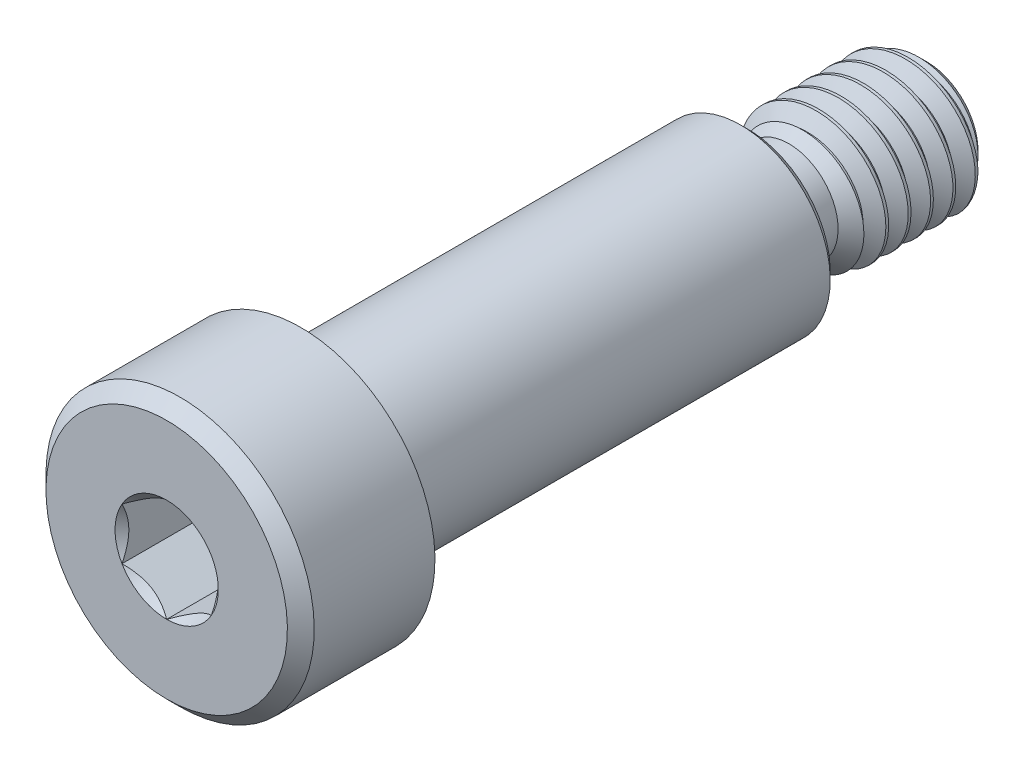
SolidWorks part; units mm, degrees
ref_plane "Front Plane" through (0, 0, 0) normal (0, 0, 1) x (1, 0, 0)
ref_plane "Top Plane" through (0, 0, 0) normal (0, 1, 0) x (1, 0, 0)
ref_plane "Right Plane" through (0, 0, 0) normal (1, 0, 0) x (0, 0, -1)
sketch "Sketch2" plane through (0, 0, 0) normal (1, 0, 0) x (0, 0, -1)
  line L0 (-13.4937, 0) -> (13.4937, 0) construction
  line L1 (-13.4937, 0) -> (-13.4937, 4.7625)
  line L2 (-13.4937, 4.7625) -> (-8.7312, 4.7625)
  line L3 (-8.7312, 4.7625) -> (-8.7313, 3.175)
  line L4 (-8.7313, 3.175) -> (7.1437, 3.175)
  line L5 (7.1437, 2.413) -> (13.4937, 2.413)
  line L6 (13.4937, 2.413) -> (13.4937, 0)
  line L7 (13.4441, 2.4989) -> (13.841, 1.8115) construction
  line L8 (13.841, 1.8115) -> (14.2379, 2.4989) construction
  line L9 (14.2379, 2.4989) -> (13.4441, 2.4989) construction
  line L10 (13.4937, 2.413) -> (14.1883, 2.413) construction
  line L11 (13.841, 2.4989) -> (13.841, 2.413) construction
  line L12 (13.841, 2.413) -> (13.841, 1.8974) construction
  line L13 (13.841, 1.8974) -> (13.841, 1.8115) construction
  line L14 (13.7914, 1.8974) -> (13.8906, 1.8974)
  line L15 (13.4689, 2.456) -> (14.2131, 2.456)
  line L16 (13.8906, 1.8974) -> (14.2131, 2.456)
  line L17 (13.7914, 1.8974) -> (13.4689, 2.456)
  line L18 (13.4937, 0) -> (13.4937, -2.413) construction
  line L19 (7.1437, -3.175) -> (7.1437, 0) construction
  line L20 (7.1437, 0) -> (7.1437, 3.175) construction
  line L21 (-13.4937, 0) -> (-13.4937, -4.7625) construction
  line L22 (8.5947, 1.7494) -> (8.5947, -1.7494) construction
  line L23 (13.4937, 0) -> (8.5947, 0) construction
  point P12 (11.5094, -2.413)
  point P22 (13.841, 2.456)
  point P23 (5.8737, 0)
  point P25 (-5.8737, 0)
  point P26 (-8.7312, -4.7625)
  point P29 (7.1437, -3.175)
  point P40 (8.5947, 0)
  dimension "Head Height" = 4.7625
  dimension "Shoulder Diameter" = 6.35
  dimension "Screw Size Decimal Equivalent" = 4.826
  dimension "Thread Length" = 6.35
  dimension "Head Diameter" = 9.525
  dimension "Pitch" = 0.7937
  dimension "D2" = 0.0992
  dimension "D1" = 1.9844
  dimension "D3" = 7.62
  dimension "D4" = 7.62
  dimension "Shoulder Length" = 15.875
  dimension "Flat" = 1.451
  dimension "Flat OD" = 3.4988
sketch "Sketch3" plane through (0, 0, 0) normal (0, 0, 1) x (1, 0, 0)
  line L1 (0, 1.8331) -> (-1.5875, 0.9165)
  line L2 (-1.5875, 0.9165) -> (-1.5875, -0.9165)
  line L3 (-1.5875, -0.9165) -> (0, -1.8331)
  line L4 (0, -1.8331) -> (1.5875, -0.9165)
  line L5 (1.5875, -0.9165) -> (1.5875, 0.9165)
  line L6 (1.5875, 0.9165) -> (0, 1.8331)
  circle A0 centre (0, 0) radius 1.5875 construction
  dimension "Drive Size" = 3.175
sketch "Sketch4" plane through (0, 0, 0) normal (1, 0, 0) x (0, 0, -1)
  line L0 (-8.7312, 4.7625) -> (-13.0175, 4.7625)
  line L1 (-13.0175, 4.7625) -> (-13.4937, 4.2862)
  line L2 (-8.7312, 4.7625) -> (-8.7313, 3.175)
  line L7 (-13.4937, 0) -> (13.4937, 0) construction
  line L8 (-8.7313, 3.175) -> (6.8897, 3.175)
  line L9 (6.8897, 3.175) -> (7.1437, 2.921)
  line L10 (7.1437, 2.921) -> (7.1437, 0)
  line L11 (7.1437, 3.175) -> (7.1437, 2.921) construction
  line L12 (7.1437, 2.921) -> (7.1437, 2.667) construction
  line L13 (7.1437, 2.667) -> (7.1437, 2.413) construction
  line L14 (-13.4937, 4.2862) -> (-13.4937, 0)
  line L16 (-13.4937, 0) -> (7.1437, 0)
  line L18 (-13.4937, 4.7625) -> (-8.7312, 4.7625) construction
  dimension "D3" = 45
  dimension "D5" = 8.5725
  dimension "D1" = 45
revolve "Revolve1" add sketch "Sketch4" angle 360 about L16
sketch "Sketch5" plane through (0, 0, 13.4937) normal (0, 0, 1) x (1, 0, 0)
  line L0 (1.5875, 0.9165) -> (0, 1.8331) construction
  line L1 (1.5875, -0.9165) -> (1.5875, 0.9165) construction
  line L2 (0, -1.8331) -> (1.5875, -0.9165) construction
  line L3 (-1.5875, -0.9165) -> (0, -1.8331) construction
  line L4 (-1.5875, 0.9165) -> (-1.5875, -0.9165) construction
  line L5 (0, 1.8331) -> (-1.5875, 0.9165) construction
  line L6 (1.5875, 0.9165) -> (0, 1.8331)
  line L7 (1.5875, -0.9165) -> (1.5875, 0.9165)
  line L8 (0, -1.8331) -> (1.5875, -0.9165)
  line L9 (-1.5875, -0.9165) -> (0, -1.8331)
  line L10 (-1.5875, 0.9165) -> (-1.5875, -0.9165)
  line L11 (0, 1.8331) -> (-1.5875, 0.9165)
extrude "Cut-Extrude1" cut sketch "Sketch5" against normal blind 3.5719
sketch "Sketch6" plane through (0, 0, 13.4937) normal (0, 0, 1) x (1, 0, 0)
  circle A0 centre (0, 0) radius 1.8331
extrude "Cut-Extrude4" cut sketch "Sketch6" against normal blind 3.5719 draft 45
sketch "Sketch7" plane through (0, 0, 0) normal (1, 0, 0) x (0, 0, -1)
  line L0 (7.1437, 2.413) -> (12.8984, 2.413)
  line L1 (7.1437, 2.413) -> (13.4937, 2.413) construction
  line L2 (12.8984, 2.413) -> (13.4937, 1.8177)
  line L3 (13.4937, 2.413) -> (13.4937, 0) construction
  line L4 (13.4937, 1.8177) -> (13.4937, 0)
  line L5 (13.4937, 0) -> (7.1437, 0)
  line L6 (7.1437, -2.921) -> (7.1437, 2.921) construction
  line L7 (7.1437, 0) -> (7.1437, 2.413)
  dimension "D1" = 45
  dimension "D2" = 0.5953
revolve "Revolve2" add sketch "Sketch7" angle 360 about L5
sketch "Sketch10" plane through (0, 0, 0) normal (1, 0, 0) x (0, 0, -1)
  line L0 (7.8073, 1.7494) -> (8.5947, 1.7494)
  line L1 (8.5947, 1.7494) -> (10.0203, 3.175)
  line L2 (10.0203, 3.175) -> (7.1437, 3.175)
  line L3 (7.1437, 3.175) -> (7.1437, 2.413)
  line L4 (7.1437, -2.921) -> (7.1437, 2.921) construction
  line L5 (13.4937, 0) -> (7.1437, 0) construction
  line L6 (-13.4937, 0) -> (13.4937, 0) construction
  line L7 (-8.7313, 3.175) -> (7.1437, 3.175) construction
  line L12 (-8.7313, 3.175) -> (-8.0962, 3.175)
  line L13 (-8.7313, 3.175) -> (-8.7313, 2.8575)
  line L14 (-8.7313, 2.8575) -> (-8.4138, 2.8575)
  line L15 (-8.0962, 3.175) -> (-8.4138, 2.8575)
  arc A0 (7.1437, 2.413) -> (7.8073, 1.7494) centre (7.8073, 2.413) ccw
  dimension "D3" = 45
  dimension "D4" = 45
  dimension "D5" = 5.715
revolve "Cut-Revolve1" cut sketch "Sketch10" angle 360 about L5
fillet "Fillet1" radius 0.1588 1 edges at (0, 2.8575, 8.7312)
sketch "Sketch15" plane through (0, 0, 0) normal (0, 0, 1) x (1, 0, 0)
  circle A0 centre (0, 0) radius 4.7625 construction
sketch "Sketch8" plane through (0, 0, -13.4937) normal (0, 0, -1) x (-1, 0, 0)
  circle A1 centre (0, 0) radius 2.413
curve "Helix/Spiral1" pitch 0.7937 height 5.6928 radius 2.413 centre (0, 0, -13.4937) axis (0, 0, 1) start towards (1, 0, 0)
sketch "Sketch9" plane through (0, 0, 0) normal (1, 0, 0) x (0, 0, -1)
  line L0 (13.7914, 1.8974) -> (13.8906, 1.8974) construction
  line L1 (13.8906, 1.8974) -> (14.2131, 2.456) construction
  line L2 (13.4689, 2.456) -> (14.2131, 2.456) construction
  line L3 (13.7914, 1.8974) -> (13.4689, 2.456) construction
  line L4 (13.7914, 1.8974) -> (13.8906, 1.8974)
  line L5 (13.8906, 1.8974) -> (14.2131, 2.456)
  line L6 (13.4689, 2.456) -> (14.2131, 2.456)
  line L7 (13.7914, 1.8974) -> (13.4689, 2.456)
ref_plane "Plane1" through (0, 0, -8.5947) normal (0, 0, 1) x (1, 0, 0)
split "Split1" trim tools "Plane1" bodies to split 138 resulting bodies 139 140
sweep "Cut-Sweep1" cut profiles "Sketch9" path "Helix/Spiral1" align with end faces yes
sketch "Sketch16" plane through (0, 0, -8.5947) normal (0, 0, -1) x (-1, 0, 0)
  circle A2 centre (0, 0) radius 1.4954
  circle A3 centre (0, 0) radius 1.4954
  dimension "D1" = 0.254
extrude "Boss-Extrude1" add sketch "Sketch16" along normal through all draft 60
equation "\"D2@Sketch2\" = \"Pitch@Sketch2\" / 8"
equation "\"D1@Sketch2\"=\"Pitch@Sketch2\"*2.5"
equation "\"D5@Sketch4\"=\"Head Diameter@Sketch2\"*0.9"
equation "\"D1@Cut-Extrude1\"=\"Head Height@Sketch2\"*0.75"
equation "\"D1@Cut-Extrude4\"=\"D1@Cut-Extrude1\""
equation "\"D2@Sketch7\" = \"Pitch@Sketch2\" * 0.75"
equation "\"D3@Helix/Spiral1\"=\"Thread Length@Sketch2\"-\"Flat@Sketch2\"+\"Pitch@Sketch2\""
equation "\"D4@Helix/Spiral1\"=\"Pitch@Sketch2\""
equation "\"D3@Sketch2\"=\"Thread Length@Sketch2\"*1.2"
equation "\"D4@Sketch2\"=\"D3@Sketch2\""
equation "\"Flat@Sketch2\"=\"Thread Length@Sketch2\"*0.2285"
equation "\"Flat OD@Sketch2\"=\"Screw Size Decimal Equivalent@Sketch2\"*.725"
equation "\"D5@Sketch10\"=\"Shoulder Diameter@Sketch2\"*.9"
equation "\"D1@Fillet1\"=\"Shoulder Diameter@Sketch2\"*.025"
